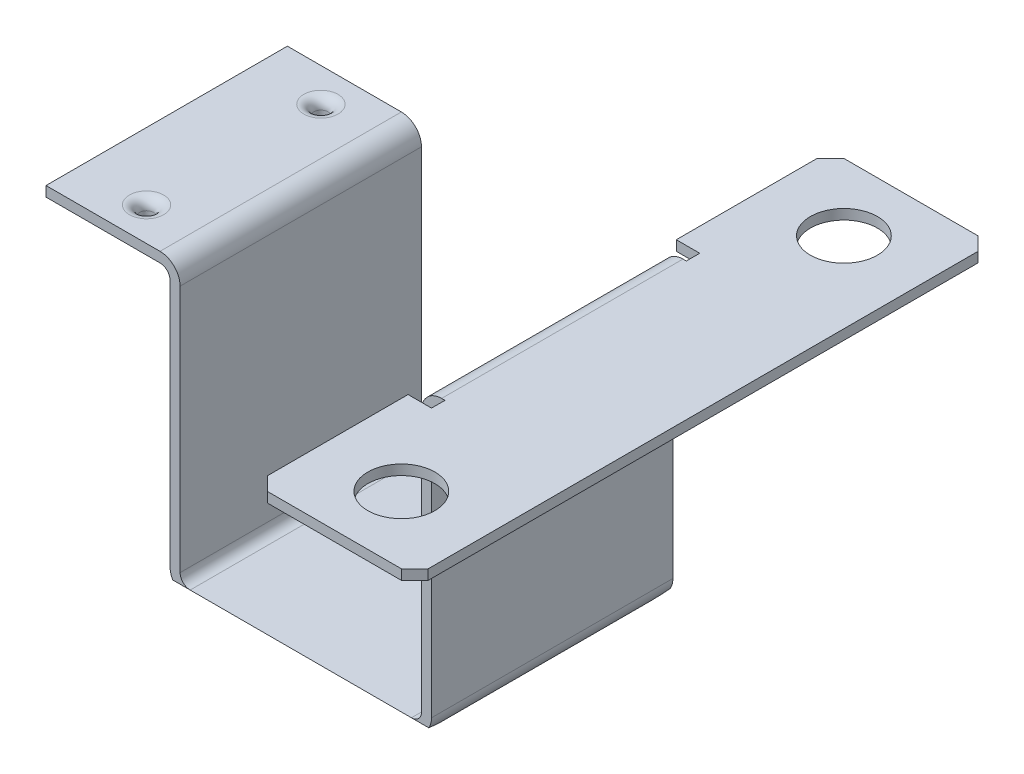
SolidWorks part; units mm, degrees
ref_plane "Спереди" through (0, 0, 0) normal (0, 0, 1) x (1, 0, 0)
ref_plane "Сверху" through (0, 0, 0) normal (0, 1, 0) x (1, 0, 0)
ref_plane "Справа" through (0, 0, 0) normal (1, 0, 0) x (0, 0, -1)
sketch "Эскиз1" plane through (0, 0, 0) normal (0, 0, 1) x (1, 0, 0)
  line L0 (-20, 41.5) -> (0, 41.5)
  line L1 (0, 41.5) -> (0, 0)
  line L2 (0, 0) -> (36, 0)
  line L3 (36, 0) -> (36, 43.5)
  line L4 (37.5, -1.5) -> (37.5, 42)
  line L5 (-1.5, -1.5) -> (37.5, -1.5)
  line L6 (-1.5, 40) -> (-1.5, -1.5)
  line L7 (-20, 40) -> (-1.5, 40)
  line L8 (-20, 40) -> (-20, 41.5)
  line L9 (60, 43.5) -> (36, 43.5)
  line L13 (37.5, 42) -> (60, 42)
  line L14 (60, 43.5) -> (60, 42)
  dimension "D1" = 36
  dimension "D2" = 1.5
  dimension "D3" = 0.5
  dimension "D4" = 56
  dimension "D5" = 1.5
  dimension "D6" = 80
  dimension "D7" = 45
extrude "Вытянуть1" add sketch "Эскиз1" along normal blind 36
sketch "Эскиз2" plane through (0, 41.5, 0) normal (0, 1, 0) x (-1, 0, 0)
  line L0 (-32.6135, 18) -> (24.3521, 18) construction
  line L1 (0, 0) -> (20, 0) construction
  line L2 (0, 36) -> (20, 36) construction
  line L3 (-36, 0) -> (0, 0) construction
  line L4 (-36, 36) -> (0, 36) construction
  line L5 (10, -5.6921) -> (10, 38.3004) construction
  line L6 (20, 36) -> (20, 0) construction
  circle A0 centre (10, 5) radius 1.05
  circle A1 centre (10, 31) radius 1.05
  dimension "D2" = 26
  dimension "D3" = 2.1
  dimension "D1" = 10
extrude "Вырез-Вытянуть1" cut sketch "Эскиз2" against normal blind 35
cosmetic thread "Условное изображение резьбы1" parameters "D1"=3, "D2"=3
cosmetic thread "Условное изображение резьбы2" parameters "D1"=3, "D2"=3
fillet "Скругление1" radius 1.5 3 edges at (36, 0, 18) (0, 0, 18) (-1.5, 40, 18)
fillet "Скругление2" radius 3 3 edges at (-1.5, -1.5, 18) (37.5, -1.5, 18) (0, 41.5, 18)
sketch "Эскиз4" plane through (-1.5, 0, 0) normal (-1, 0, 0) x (0, 0, 1)
  line L0 (36, 0) -> (30.4019, -1.5)
  line L1 (36, -1.5) -> (0, -1.5) construction
  line L2 (18, 25.5007) -> (18, -4.2731) construction
  line L3 (36, 38.5) -> (36, 1.5) construction
  line L4 (0, 38.5) -> (0, 1.5) construction
  line L5 (0, 0) -> (5.5981, -1.5)
  line L6 (36, 0) -> (36, -8.931)
  line L7 (36, -8.931) -> (0, -9.7268)
  line L8 (0, -9.7268) -> (0, 0)
  line L9 (5.5981, -1.5) -> (30.4019, -1.5)
  dimension "D1" = 15
extrude "Вырез-Вытянуть5" cut sketch "Эскиз4" against normal blind 50
sketch "Эскиз5" plane through (0, 43.5, 0) normal (0, 1, 0) x (-1, 0, 0)
  line L0 (-63.6407, 18) -> (21.0689, 18) construction
  line L1 (-60, 0) -> (-36, 0) construction
  line L2 (-60, 36) -> (-36, 36) construction
  line L3 (-60, 36) -> (-60, 0) construction
  line L4 (-36, -25) -> (-60, -25)
  line L5 (-36, -25) -> (-36, 61)
  line L6 (-36, 61) -> (-60, 61)
  line L7 (-60, -25) -> (-60, 61)
  line L8 (-36, 36) -> (-36, 0) construction
  line L9 (-48, -35.3655) -> (-48, 64.7752) construction
  circle A0 centre (-48, -15) radius 5
  circle A1 centre (-48, 51) radius 5
  dimension "D1" = 10
  dimension "D2" = 33
  dimension "D3" = 86
extrude "Вытянуть2" add sketch "Эскиз5" against normal blind 1.5
sketch "Эскиз6" plane through (36, 0, 0) normal (-1, 0, 0) x (0, 0, 1)
  line L0 (36, 42) -> (36, 1.5) construction
  line L1 (36, 39.7705) -> (38, 39.7705)
  line L2 (36, 39.7705) -> (36, 46.1069)
  line L3 (36, 46.1069) -> (38, 46.1069)
  line L4 (38, 39.7705) -> (38, 46.1069)
  line L5 (18, 50.7661) -> (18, 23.1839) construction
  line L6 (0, 42) -> (0, 1.5) construction
  line L7 (0, 39.7705) -> (0, 46.1069)
  line L8 (0, 46.1069) -> (-2, 46.1069)
  line L9 (-2, 39.7705) -> (-2, 46.1069)
  line L10 (0, 39.7705) -> (-2, 39.7705)
  dimension "D1" = 2
extrude "Вырез-Вытянуть6" cut sketch "Эскиз6" against normal blind 3.5
fillet "Скругление3" radius 1.5 1 edges at (37.5, 42, 18)
fillet "Скругление4" radius 3 1 edges at (36, 43.5, 18)
sketch "Эскиз7" plane through (0, 40, 0) normal (0, -1, 0) x (1, 0, 0)
  circle A0 centre (-10, 31) radius 2.5
  circle A1 centre (-10, 5) radius 2.5
  circle A2 centre (-10, 31) radius 1.05 construction
  circle A3 centre (-10, 31) radius 1.05
  circle A4 centre (-10, 5) radius 1.05 construction
  circle A5 centre (-10, 5) radius 1.05
  dimension "D1" = 5
extrude "Вытянуть3" add sketch "Эскиз7" along normal blind 1.5
fillet "Скругление5" radius 1.5 4 edges at (-10, 41.5, 6.05) (-10, 41.5, 32.05) (-10, 40, 7.5) (-10, 40, 33.5)
chamfer "Фаска1" distance 2 angle 45 4 edges at (36, 42.75, 61) (60, 42.75, 61) (60, 42.75, -25) (36, 42.75, -25)
